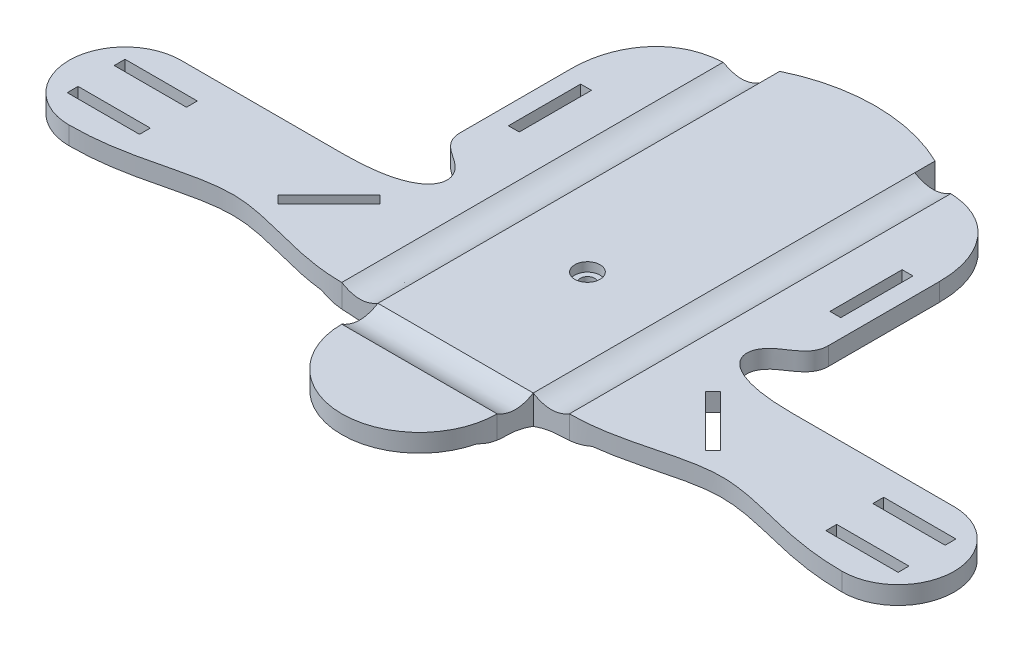
SolidWorks part; units mm, degrees
ref_plane "Front Plane" through (0, 0, 0) normal (0, 0, 1) x (1, 0, 0)
ref_plane "Top Plane" through (0, 0, 0) normal (0, 1, 0) x (1, 0, 0)
ref_plane "Right Plane" through (0, 0, 0) normal (1, 0, 0) x (0, 0, -1)
sketch "Foot Measurements" plane through (0, 0, 0) normal (0, 1, 0) x (1, 0, 0)
  line L0 (0, 0) -> (85, 0) construction
  line L1 (0, 0) -> (0, 145) construction
  line L2 (12.5, 115) -> (72.5, 115) construction
  line L4 (21, 83) -> (21, 0) construction
  line L5 (72.5, 115) -> (72.5, 0) construction
  line L6 (0, 145) -> (85, 145) construction
  line L7 (85, 145) -> (85, 0) construction
  line L8 (0, -100) -> (250, -100) construction
  line L9 (0, -100) -> (173, -100) construction
  line L11 (64, 0) -> (64, 83) construction
  line L12 (64, 83) -> (21, 83) construction
  line L13 (12.5, 115) -> (12.5, 0) construction
  dimension "D1" = 83
  dimension "D2" = 12.5
  dimension "D3" = 43
  dimension "D4" = 145
  dimension "D6" = 115
  dimension "D7" = 8.5
  dimension "D8" = 12.5
  dimension "D9" = 8.5
sketch "Sandal Design" plane through (0, 0, 0) normal (0, 1, 0) x (1, 0, 0)
  line L0 (42.5, 83) -> (42.5, 101.8434) construction
  line L1 (64, 83) -> (21, 83) construction
  line L2 (101.6421, 10) -> (103.7635, 12.1213)
  line L3 (157.5, 23.5018) -> (137.5, 23.5018)
  line L4 (157.5, 23.5018) -> (157.5, 20.5018)
  line L5 (0, 0) -> (85, 0) construction
  line L6 (137.5, 7.5018) -> (137.5, 10.5018)
  line L7 (-4.6213, 26.2635) -> (-2.5, 24.1421)
  line L8 (-4.6213, 26.2635) -> (-18.7635, 12.1213)
  line L9 (12.5, 105.6182) -> (21, 105.6182)
  line L10 (-64.5, 31.0018) -> (-19.5, 31.0018)
  line L11 (-2.5, 24.1421) -> (-16.6421, 10)
  line L12 (-52.5, 23.5018) -> (-52.5, 20.5018)
  line L13 (157.5, 10.5018) -> (137.5, 10.5018)
  line L14 (-72.5, 20.5018) -> (-52.5, 20.5018)
  line L15 (-72.5, 7.5018) -> (-52.5, 7.5018)
  line L16 (-72.5, 7.5018) -> (-72.5, 10.5018)
  line L17 (-72.5, 10.5018) -> (-52.5, 10.5018)
  line L18 (-52.5, 7.5018) -> (-52.5, 10.5018)
  line L19 (-72.5, 23.5018) -> (-72.5, 20.5018)
  line L20 (-72.5, 23.5018) -> (-52.5, 23.5018)
  line L21 (-16.6421, 10) -> (-18.7635, 12.1213)
  line L22 (157.5, 7.5018) -> (157.5, 10.5018)
  line L23 (12.5, 115) -> (12.5, 0) construction
  line L24 (157.5, 7.5018) -> (137.5, 7.5018)
  line L25 (64, 111.2308) -> (64, 105.6182)
  line L26 (72.5, 105.6182) -> (64, 105.6182)
  line L27 (93.5, 83) -> (93.5, 52.1918)
  line L29 (157.5, 20.5018) -> (137.5, 20.5018)
  line L30 (137.5, 23.5018) -> (137.5, 20.5018)
  line L32 (87.5, 24.1421) -> (101.6421, 10)
  line L38 (104.5, 31.0018) -> (149.5, 31.0018)
  line L39 (89.6213, 26.2635) -> (103.7635, 12.1213)
  line L40 (89.6213, 26.2635) -> (87.5, 24.1421)
  line L41 (11, 0) -> (21, 0)
  line L42 (21, 0) -> (21, -10)
  line L43 (64, 0) -> (64, -10)
  line L44 (64, 0) -> (74, 0)
  line L45 (21, 83) -> (21, 111.2308) construction
  line L46 (64, 83) -> (64, 111.2308) construction
  line L47 (-0.5, 80.6182) -> (-3.5, 80.6182)
  line L48 (-0.5, 80.6182) -> (-0.5, 60.6182)
  line L49 (-0.5, 60.6182) -> (-3.5, 60.6182)
  line L50 (-3.5, 80.6182) -> (-3.5, 60.6182)
  line L51 (-8.5, 83) -> (-8.5, 52.1918)
  line L54 (21, 111.2308) -> (21, 105.6182)
  line L57 (88.5, 80.6182) -> (88.5, 60.6182)
  line L58 (85.5, 60.6182) -> (88.5, 60.6182)
  line L59 (85.5, 80.6182) -> (85.5, 60.6182)
  line L60 (85.5, 80.6182) -> (88.5, 80.6182)
  arc A0 (149.5, 31.0018) -> (149.4998, 0.0018) centre (149.5, 15.5018) cw
  arc A1 (21, -10) -> (64, -10) centre (42.5, -10) ccw
  arc A4 (-64.5, 31.0018) -> (-64.4998, 0.0018) centre (-64.5, 15.5018) ccw
  arc A5 (64, 111.2308) -> (21, 111.2308) centre (42.5, 67) ccw
  spline S0 degree 3 poles (11, 0) (-2.4941, 0) (-26.3478, 12.0693) (-46.9264, 0.002) (-64.4998, 0.0018) knots 0 0 0 0 0.462856 1 1 1 1
  spline S1 degree 3 poles (-8.5, 52.1918) (-8.5, 47.5404) (4.8954, 43.2018) (1.7687, 31.0018) (-19.5, 31.0018) knots 0 0 0 0 0.331226 1 1 1 1
  spline S2 degree 3 poles (93.5, 83) (93.5, 91.1968) (88.2042, 102.2246) (77.5635, 105.6182) (72.5, 105.6182) knots 0 0 0 0 0.612936 1 1 1 1
  spline S3 degree 3 poles (74, 0) (87.4941, 0) (111.3478, 12.0693) (131.9264, 0.002) (149.4998, 0.0018) knots 0 0 0 0 0.462856 1 1 1 1
  spline S4 degree 3 poles (-8.5, 83) (-8.5, 91.1968) (-3.2042, 102.2246) (7.4365, 105.6182) (12.5, 105.6182) knots 0 0 0 0 0.612936 1 1 1 1
  spline S5 degree 3 poles (93.5, 52.1918) (93.5, 47.5404) (80.1046, 43.2018) (83.2313, 31.0018) (104.5, 31.0018) knots 0 0 0 0 0.331226 1 1 1 1
  dimension "D11" = 8
  dimension "D17" = 15
  dimension "D18" = 45
  dimension "D19" = 20
  dimension "D5" = 3
  dimension "D6" = 10
  dimension "D9" = 10
  dimension "D13" = 20
  dimension "D10" = 7.5
  dimension "D12" = 15.5
  dimension "D24" = 25
  dimension "D23" = 3
  dimension "D3" = 25
  dimension "D4" = 20
  dimension "D7" = 7.5
  dimension "D8" = 65
  dimension "D14" = 3
  dimension "D15" = 10
  dimension "D16" = 45
  dimension "D25" = 10
  dimension "D26" = 5
extrude "Boss-Extrude1" add sketch "Sandal Design" along normal blind 8
sketch "Sketch4" plane through (0, 0, 0) normal (0, -1, 0) x (1, 0, 0)
  line L0 (64, -15.5775) -> (64, -57.4225)
  line L1 (21, -15.5775) -> (21, -57.4225)
  arc A0 (21, -57.4225) -> (64, -57.4225) centre (42.5, -36.5) ccw
  arc A1 (64, -15.5775) -> (21, -15.5775) centre (42.5, -36.5) ccw
  dimension "D1" = 30
  dimension "D2" = 41.845
extrude "Boss-Extrude2" add sketch "Sketch4" along normal blind 2.5
sketch "Sketch6" plane through (0, -2.5, 0) normal (0, -1, 0) x (1, 0, 0)
  circle A0 centre (42.5, -36.5) radius 2
extrude "Cut-Extrude3" cut sketch "Sketch6" against normal up to next
sketch "Sketch7" plane through (0, 8, 0) normal (0, 1, 0) x (1, 0, 0)
  circle A0 centre (42.5, 36.5) radius 3.5
extrude "Cut-Extrude4" cut sketch "Sketch7" against normal blind 2.5
sketch "Sketch8" plane through (0, 0, 0) normal (0, 0, 1) x (1, 0, 0)
  line L0 (42.5, 8) -> (42.5, 0) construction
  line L2 (16, 8) -> (16, 6.5) construction
  line L3 (-80, 0) -> (21, 0)
  line L4 (11, 8) -> (21, 8) construction
  line L5 (11, 8) -> (21, 8)
  line L6 (64, 8) -> (21, 8) construction
  line L7 (5, 3) -> (21, 3) construction
  line L8 (5, 3) -> (-80, 3)
  line L9 (-80, 3) -> (-80, 0)
  line L10 (21, 8) -> (21, 0) construction
  line L11 (0, 0) -> (85, 0) construction
  line L13 (13, 3) -> (13, 1.5) construction
  line L15 (69, 8) -> (69, 6.5) construction
  line L16 (165, 3) -> (165, 0)
  line L17 (80, 3) -> (165, 3)
  line L18 (74, 8) -> (64, 8)
  line L19 (165, 0) -> (64, 0)
  spline S0 degree 2 poles (11, 8) (16, 5) (21, 8) knots 0 0 0 1 1 1
  spline S1 degree 2 poles (21, 0) (17, 1.5) (13, 1.5) knots 0 0 0 0.5 0.5 0.5
  spline S2 degree 3 poles (5, 3) (7.6685, 1.9993) (10.3371, 1.4993) (13.0056, 1.5) knots 0 0 0 0 0.50035 0.50035 0.50035 0.50035
  spline S3 degree 2 poles (64, 0) (68, 1.5) (72, 1.5) knots 0 0 0 0.5 0.5 0.5
  spline S4 degree 3 poles (80, 3) (77.3315, 1.9993) (74.6629, 1.4993) (71.9944, 1.5) knots 0 0 0 0 0.50035 0.50035 0.50035 0.50035
  spline S5 degree 2 poles (74, 8) (69, 5) (64, 8) knots 0 0 0 1 1 1
  dimension "D2" = 3
extrude "Cut-Extrude5" cut sketch "Sketch8" against normal through all both and the other way through all contours L3 L8 L9 | L19 L16 L17 | S5 L18 | L5 S0 region at (-33.328, 1.4484, 0) region at (16, 7.4, 0) region at (118.328, 1.4484, 0) region at (69, 7.4, 0)
sketch "Sketch9" plane through (0, 0, 0) normal (1, 0, 0) x (0, 0, -1)
  line L0 (-5, 8) -> (-5, 3) construction
  line L1 (-10, 8) -> (0, 8) construction
  line L2 (-15, 3) -> (0, 3) construction
  line L4 (-10, 8) -> (0.0018, 8)
  line L5 (-31.5, 0) -> (-31.5, 3)
  line L6 (-31.5, 8) -> (-31.5, 0) construction
  line L7 (-31.5, 3) -> (-15, 3)
  line L8 (-31.5, 0) -> (-10, 0) construction
  line L9 (-31.5, 0) -> (0, 0)
  line L10 (0, 8) -> (0, 0) construction
  spline S0 degree 2 poles (0, 0) (-3.75, 1.5) (-7.5, 1.5) knots 0 0 0 0.5 0.5 0.5
  spline S1 degree 2 poles (-10, 8) (-4.9993, 5) (0.0018, 8) knots 0 0 0 1 1 1
  spline S2 degree 3 poles (-15, 3) (-12.4982, 1.9993) (-9.9965, 1.4993) (-7.4947, 1.5) knots 0 0 0 0 0.50035 0.50035 0.50035 0.50035
  dimension "D2" = 1.5
  dimension "D3" = 3
extrude "Cut-Extrude6" cut sketch "Sketch9" against normal through all both and the other way through all contours L4 S1 | L9 S0 L7 L5 region at (0, 7.4, 4.9992) region at (0, 1.3125, 18.9141)
ref_plane "Plane1" through (42.5, 0, 0) normal (1, 0, 0) x (0, 0, -1)
sketch "Sketch12" plane through (42.5, 0, 0) normal (1, 0, 0) x (0, 0, -1)
  line L0 (36.5, -2.5) -> (36.5, 0) construction
  line L4 (57.4225, -2.5) -> (15.5775, -2.5) construction
  line L5 (0, 0) -> (145, 0) construction
  line L6 (34.5, 0) -> (34.5, -2.5)
  line L7 (34.5, 0) -> (15.5775, 0)
  line L8 (15.5775, 0) -> (6.5, -2.5)
  line L9 (6.5, -2.5) -> (34.5, -2.5)
  dimension "D1" = 2
revolve "Revolve1" add sketch "Sketch12" angle 360 about L0 region at (42.5, -1.3306, -22.623)
